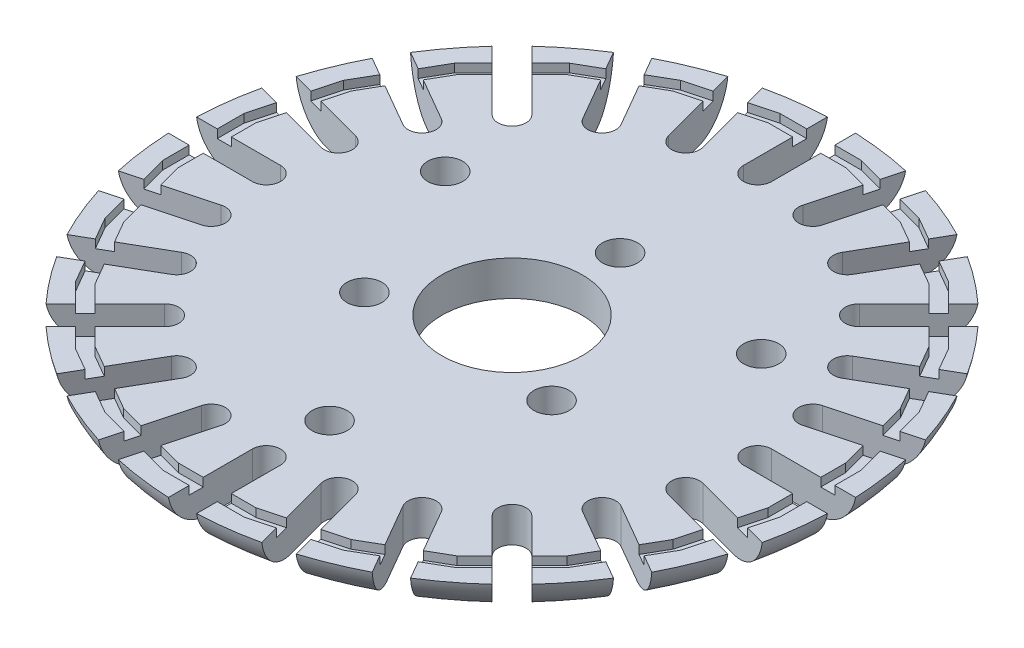
SolidWorks part; units mm, degrees
ref_plane "Plano frontal" through (0, 0, 0) normal (0, 0, 1) x (1, 0, 0)
ref_plane "Plano superior" through (0, 0, 0) normal (0, 1, 0) x (1, 0, 0)
ref_plane "Plano direito" through (0, 0, 0) normal (1, 0, 0) x (0, 0, -1)
sketch "Esboço1" plane through (0, 0, 0) normal (0, 1, 0) x (1, 0, 0)
  circle A0 centre (0, 0) radius 23.5
  dimension "D1" = 47
extrude "Ressalto-extrusão1" add sketch "Esboço1" along normal blind 2.5
fillet "Filete1" radius 3 1 edges at (0, 0, 23.5)
sketch "Esboço2" plane through (0, 2.5, 0) normal (0, 1, 0) x (1, 0, 0)
  line L0 (0, 0) -> (0, 23.9078) construction
  line L2 (1, 17.5) -> (1, 23.5)
  line L3 (1, 23.5) -> (-1, 23.5)
  line L4 (0, 23.5) -> (7.8408, 23.5) construction
  line L5 (-1, 17.5) -> (-1, 23.5)
  arc A0 (-1, 17.5) -> (1, 17.5) centre (0, 17.5) ccw
  circle A3 centre (0, 0) radius 23.5 construction
  point P12 (0, 16.5)
  dimension "D2" = 6
  dimension "D1" = 1
extrude "Corte-extrusão1" cut sketch "Esboço2" against normal through all
pattern_circular "PadrãoCircular1" count 24 over 360 about axis through (0, 2.5, 0) along (0, 1, 0) of "Corte-extrusão1"
sketch "Esboço4" plane through (0, 2.5, 0) normal (0, 1, 0) x (1, 0, 0)
  line L0 (0, 0) -> (-3.0674, 23.299) construction
  line L1 (0, 0) -> (3.0674, 23.299) construction
  line L2 (-2.8964, 22) -> (2.8964, 22)
  line L3 (2.8964, 22) -> (2.7647, 21)
  line L4 (2.7647, 21) -> (-2.7647, 21)
  line L5 (-2.7647, 21) -> (-2.8964, 22)
  arc A2 (5.1108, 22.9375) -> (1, 23.4787) centre (0, 0) ccw construction
  arc A3 (-1, 23.4787) -> (-5.1108, 22.9375) centre (0, 0) ccw construction
  dimension "D1" = 1
  dimension "D2" = 21
extrude "Corte-extrusão2" cut sketch "Esboço4" against normal blind 0.6
pattern_circular "PadrãoCircular2" count 24 over 360 about axis through (0, 2.5, 0) along (0, 1, 0) of "Corte-extrusão2"
sketch "Esboço5" plane through (0, 2.5, 0) normal (0, 1, 0) x (1, 0, 0)
  circle A0 centre (0, 0) radius 5
  dimension "D1" = 10
extrude "Corte-extrusão3" cut sketch "Esboço5" against normal through all
sketch "Esboço6" plane through (0, 2.5, 0) normal (0, 1, 0) x (1, 0, 0)
  circle A1 centre (0, 7.7) radius 1.25
  circle A2 centre (-6.6684, -3.85) radius 1.25
  circle A3 centre (6.6684, -3.85) radius 1.25
  circle A4 centre (-11.2583, 6.5) radius 1.25
  circle A5 centre (11.2583, 6.5) radius 1.25
  circle A6 centre (0, -13) radius 1.25
  dimension "D1" = 2.5
  dimension "D2" = 7.7
  dimension "D5" = 2.5
  dimension "D3" = 7.7
  dimension "D4" = 7.7
extrude "Corte-extrusão5" cut sketch "Esboço6" against normal blind 2.5
